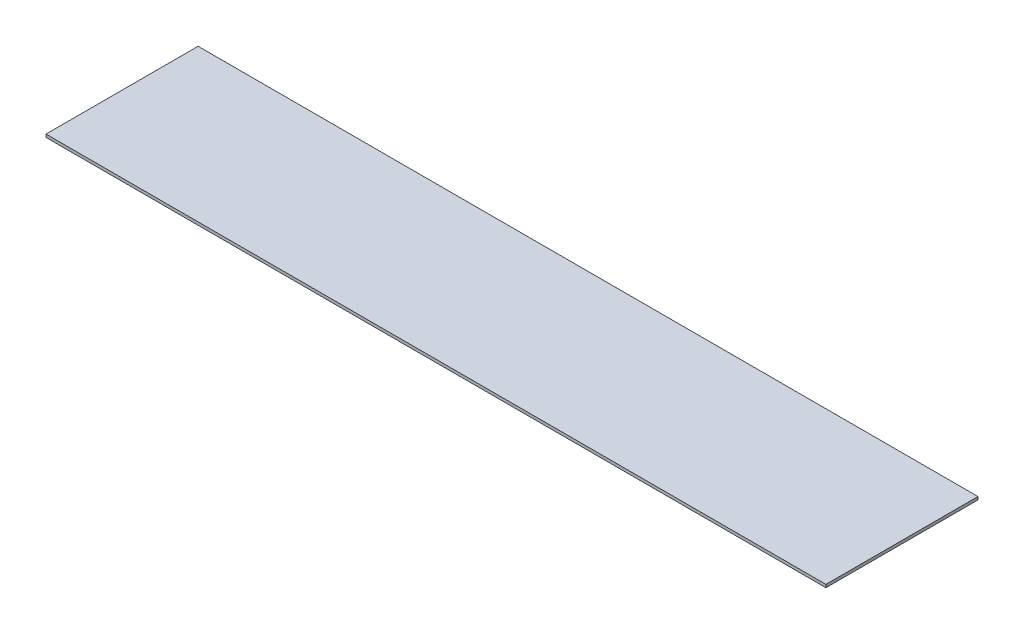
SolidWorks part; units mm, degrees
ref_plane "Front Plane" through (0, 0, 0) normal (0, 0, 1) x (1, 0, 0)
ref_plane "Top Plane" through (0, 0, 0) normal (0, 1, 0) x (1, 0, 0)
ref_plane "Right Plane" through (0, 0, 0) normal (1, 0, 0) x (0, 0, -1)
sketch "Sketch1" plane through (0, 0, 0) normal (0, 1, 0) x (1, 0, 0)
  line L1 (0, 0) -> (800, 0)
  line L2 (0, 0) -> (0, 156)
  line L3 (0, 156) -> (800, 156)
  line L4 (800, 0) -> (800, 156)
  dimension "D1" = 800
  dimension "D2" = 156
extrude "Boss-Extrude1" add sketch "Sketch1" along normal blind 3
